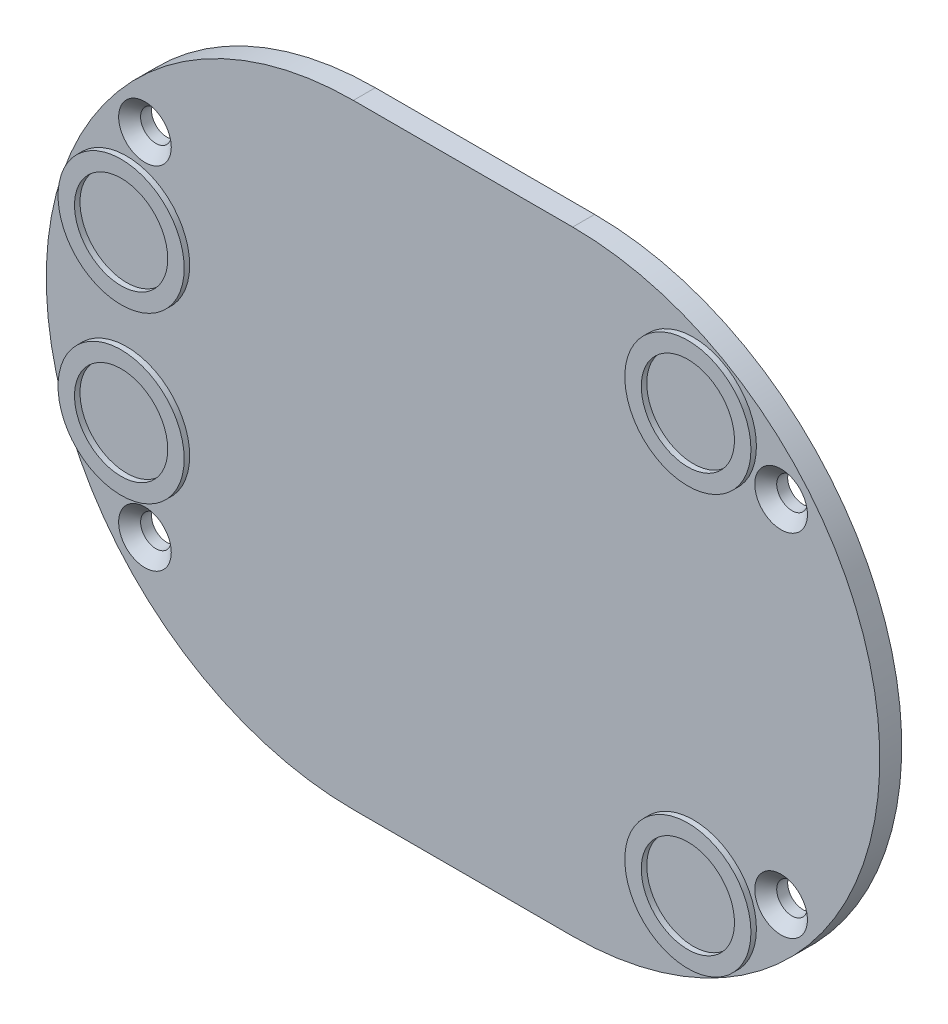
SolidWorks part; units mm, degrees
material "POM 乙缩醛共聚物"
ref_plane "前视基准面" through (0, 0, 0) normal (0, 0, 1) x (1, 0, 0)
ref_plane "上视基准面" through (0, 0, 0) normal (0, 1, 0) x (1, 0, 0)
ref_plane "右视基准面" through (0, 0, 0) normal (1, 0, 0) x (0, 0, -1)
sketch "草图3" plane through (0, 0, 0) normal (0, 0, 1) x (1, 0, 0)
  line L2 (10, -28) -> (-10, -28)
  line L3 (-10, 28) -> (10, 28)
  arc A2 (-10, 28) -> (-10, -28) centre (-10, 0) ccw
  arc A3 (10, -28) -> (10, 28) centre (10, 0) ccw
extrude "凸台-拉伸2" add sketch "草图3" along normal blind 2 contours L3 A3 L2 A2
hole_wizard "打孔尺寸(%根据十字)槽沉头自攻螺钉的类型0" positions "草图5" profile "草图6" countersink size "ST2.2" standard "GB"
sketch "草图5" plane through (0, 0, 2) normal (0, 0, 1) x (1, 0, 0)
  line L1 (12.1906, 0) -> (-13.0853, 0) construction
  line L2 (14.2037, 0) -> (-13.0853, 0) construction
  line L5 (-29, 16) -> (29, 16)
  line L6 (-29, 16) -> (-29, -16)
  line L7 (-29, -16) -> (29, -16)
  line L8 (29, 16) -> (29, -16)
  line L9 (0, -7.6396) -> (0, 21.327) construction
  point P0 (-29, 16)
  point P2 (-29, -16)
  point P4 (29, 16)
  point P6 (29, -16)
  dimension "D1" = 32
  dimension "D2" = 58
sketch "草图6" plane through (-29, 16, 2) normal (1, 0, 0) x (0, -1, 0)
  line L0 (0, 0) -> (0, 10.9412)
  line L1 (0, 10.9412) -> (1.4, 10.1)
  line L2 (1.4, 10.1) -> (1.4, 1)
  line L3 (1.4, 1) -> (2.4, 0)
  line L5 (2.4, 0) -> (0, 0)
  line L6 (-1.4, 1) -> (-2.4, 0) construction
  line L10 (0, 10.9412) -> (-1.4, 10.1) construction
  line L11 (0, -6.35) -> (0, 107.95) construction
  dimension "孔直径" = 2.8
  dimension "孔深度" = 10.1
  dimension "近端锥形沉头孔直径" = 4.8
  dimension "近端锥形沉头孔角度" = 90
  dimension "导头角度" = 118
sketch "草图7" plane through (0, 0, 2) normal (0, 0, 1) x (1, 0, 0)
  circle A0 centre (-30.6732, 7.5244) radius 4.25
  circle A1 centre (-30.6732, -7.5244) radius 4.25
  circle A2 centre (21, -19.0526) radius 4.25
  circle A3 centre (21, 19.0526) radius 4.25
  dimension "D1" = 8.5
extrude "拉伸-薄壁1" add sketch "草图7" along normal blind 0.5 thin thin type one direction wall 1.5
sketch "草图10" plane through (0, 0, 2) normal (0, 0, 1) x (1, 0, 0)
  arc A0 (-24.2149, -8.3777) -> (-8.555, -16.4366) centre (-10, 0) ccw
  dimension "D1" = 16.5
extrude "拉伸-薄壁2" add sketch "草图10" against normal blind 21.5 thin thin type one direction wall 2.5
chamfer "倒角1" distance 1 angle 45 2 edges at (-18.6941, -16.8942, 0) (-17.5501, -14.6713, 0)
chamfer "倒角2" distance 2 angle 45 1 edges at (-24.2149, -8.3777, -10.25)
chamfer "倒角3" distance 2 angle 45 1 edges at (-24.6457, -8.6316, -1.5)
